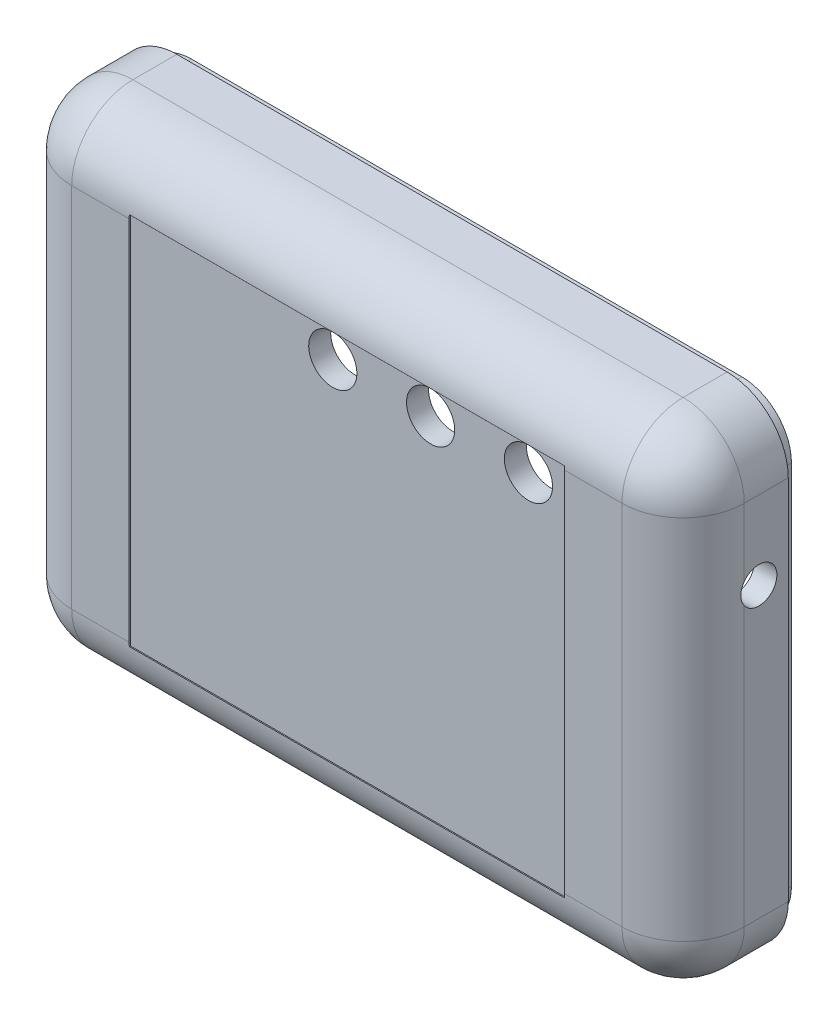
SolidWorks part; units mm, degrees
material "ABS"
ref_plane "Front Plane" through (0, 0, 0) normal (0, 0, 1) x (1, 0, 0)
ref_plane "Top Plane" through (0, 0, 0) normal (0, 1, 0) x (1, 0, 0)
ref_plane "Right Plane" through (0, 0, 0) normal (1, 0, 0) x (0, 0, -1)
ref_plane "Plane1" through (0, 0, 9.652) normal (0, 0, -1) x (-1, 0, 0)
sketch "Sketch1" plane through (0, 0, 9.652) normal (0, 0, -1) x (-1, 0, 0)
  line L0 (-146.2852, 11.5363) -> (-76.4352, 11.5363)
  line L1 (-76.4352, 11.5363) -> (-76.4352, 62.3363)
  line L2 (-76.4352, 62.3363) -> (-146.2852, 62.3363)
  line L3 (-146.2852, 62.3363) -> (-146.2852, 11.5363)
extrude "Boss-Extrude1" add sketch "Sketch1" against normal blind 10.922
sketch "Sketch2" plane through (0, 0, 9.652) normal (0, 0, -1) x (-1, 0, 0)
  line L0 (-77.629, 23.0298) -> (-77.629, 12.7301)
  line L1 (-77.629, 12.7301) -> (-145.0914, 12.7301)
  line L2 (-145.0914, 12.7301) -> (-145.0914, 61.1425)
  line L3 (-145.0914, 61.1425) -> (-77.629, 61.1425)
  line L4 (-77.629, 61.1425) -> (-77.629, 54.7798)
  line L5 (-77.629, 54.7798) -> (-143.9484, 54.7798)
  line L6 (-143.9484, 54.7798) -> (-143.9484, 23.0298)
  line L7 (-143.9484, 23.0298) -> (-77.629, 23.0298)
extrude "Boss-Extrude2" add sketch "Sketch2" along normal blind 1.524
ref_plane "Plane2" through (0, 0, 16.764) normal (0, 0, 1) x (1, 0, 0)
sketch "Sketch4" plane through (0, 0, 16.764) normal (0, 0, 1) x (1, 0, 0)
  line L0 (143.9484, 54.7798) -> (76.4352, 54.7798)
  line L1 (76.4352, 54.7798) -> (76.4352, 23.0298)
  line L2 (76.4352, 23.0298) -> (143.9484, 23.0298)
  line L3 (143.9484, 23.0298) -> (143.9484, 54.7798)
extrude "Cut-Extrude1" cut sketch "Sketch4" against normal up to surface up to plane "Plane1"
sketch "Sketch5" plane through (0, 0, 16.764) normal (0, 0, -1) x (-1, 0, 0)
  line L0 (-143.9484, 54.7798) -> (-143.9484, 23.0298)
  line L1 (-143.9484, 23.0298) -> (-78.772, 23.0298)
  line L2 (-78.772, 23.0298) -> (-78.772, 54.7798)
  line L3 (-78.772, 54.7798) -> (-143.9484, 54.7798)
extrude "Cut-Extrude2" cut sketch "Sketch5" against normal blind 1.397
ref_plane "Plane3" through (0, 13.8731, 0) normal (0, -1, 0) x (1, 0, 0)
sketch "Sketch6" plane through (0, 13.8731, 0) normal (0, -1, 0) x (1, 0, 0)
  line L0 (78.772, 8.128) -> (143.9484, 8.128)
  line L1 (143.9484, 8.128) -> (143.9484, 18.161)
  line L2 (143.9484, 18.161) -> (78.772, 18.161)
  line L3 (78.772, 18.161) -> (78.772, 8.128)
extrude "Cut-Extrude3" cut sketch "Sketch6" against normal up to next
ref_plane "Plane4" through (0, 59.9995, 0) normal (0, 1, 0) x (1, 0, 0)
sketch "Sketch7" plane through (0, 59.9995, 0) normal (0, 1, 0) x (1, 0, 0)
  line L0 (78.772, -18.161) -> (143.9484, -18.161)
  line L1 (143.9484, -18.161) -> (143.9484, -8.128)
  line L2 (143.9484, -8.128) -> (78.772, -8.128)
  line L3 (78.772, -8.128) -> (78.772, -18.161)
extrude "Cut-Extrude4" cut sketch "Sketch7" against normal up to next
sketch "Sketch8" plane through (0, 0, 20.574) normal (0, 0, 1) x (1, 0, 0)
  line L0 (133.9662, 56.3673) -> (88.7542, 56.3673)
  line L1 (88.7542, 56.3673) -> (88.7542, 17.5053)
  line L2 (88.7542, 17.5053) -> (133.9662, 17.5053)
  line L3 (133.9662, 17.5053) -> (133.9662, 56.3673)
extrude "Cut-Extrude5" cut sketch "Sketch8" against normal blind 0.127
ref_plane "Plane5" through (0, 19.4738, 0) normal (0, -1, 0) x (1, 0, 0)
sketch "Sketch9" plane through (0, 19.4738, 0) normal (0, -1, 0) x (1, 0, 0)
  line L0 (86.7603, 18.161) -> (84.3727, 18.161)
  line L1 (84.3727, 18.161) -> (84.3727, 8.89)
  line L2 (84.3727, 8.89) -> (86.7603, 8.89)
  line L3 (86.7603, 8.89) -> (86.7603, 18.161)
  line L4 (84.3727, 18.161) -> (84.3727, 8.89) construction
revolve "Revolve1" add sketch "Sketch9" angle 360 about L4 reverse direction yes
ref_plane "Plane6" through (0, 54.3988, 0) normal (0, -1, 0) x (1, 0, 0)
sketch "Sketch10" plane through (0, 54.3988, 0) normal (0, -1, 0) x (1, 0, 0)
  line L0 (140.7353, 18.161) -> (138.3477, 18.161)
  line L1 (138.3477, 18.161) -> (138.3477, 8.89)
  line L2 (138.3477, 8.89) -> (140.7353, 8.89)
  line L3 (140.7353, 8.89) -> (140.7353, 18.161)
  line L4 (138.3477, 18.161) -> (138.3477, 8.89) construction
revolve "Revolve2" add sketch "Sketch10" angle 360 about L4 reverse direction yes
hole_wizard "Hole1" positions "Sketch12" profile "Sketch11" legacy
sketch "Sketch12" plane through (0, 0, 18.161) normal (0, 0, -1) x (-1, 0, 0)
  point P0 (-130.0927, 53.7638)
  point P1 (-119.9327, 53.7638)
  point P2 (-109.7727, 53.7638)
sketch "Sketch11" plane through (130.0927, 53.7638, 18.161) normal (1, 0, 0) x (0, 1, 0)
  line L0 (0, 0) -> (0, 2.413)
  line L1 (0, 2.413) -> (2.5019, 2.413)
  line L2 (2.5019, 2.413) -> (2.5019, 0)
  line L3 (2.5019, 0) -> (0, 0)
  line L4 (0, 110) -> (0, -10) construction
  dimension "Diameter" = 5.0038
  dimension "Depth" = 2.413
hole_wizard "M2 Clearance Hole1" positions "Sketch14" profile "Sketch13" hole size "M2" standard "ANSI Metric"
sketch "Sketch14" plane through (0, 0, 8.89) normal (0, 0, -1) x (-1, 0, 0)
  point P0 (-138.3477, 54.3988)
  point P1 (-84.3727, 19.4738)
sketch "Sketch13" plane through (138.3477, 54.3988, 8.89) normal (1, 0, 0) x (0, 1, 0)
  line L0 (0, 0) -> (0, 9.271)
  line L1 (0, 9.271) -> (1.143, 9.271)
  line L2 (1.143, 9.271) -> (1.143, 0)
  line L5 (1.143, 0) -> (0, 0)
  line L10 (0, 9.271) -> (-1.143, 9.271) construction
  line L11 (0, -6.35) -> (0, 107.95) construction
  dimension "Hole Dia." = 2.286
  dimension "Hole Depth" = 9.271
  dimension "Drill Angle" = 180
hole_wizard "M3.5 Clearance Hole1" positions "Sketch16" profile "Sketch15" hole size "M3.5" standard "ANSI Metric"
sketch "Sketch16" plane through (143.9484, 0, 0) normal (-1, 0, 0) x (0, 0, 1)
  point P0 (12.7, 47.8583)
sketch "Sketch15" plane through (143.9484, 47.8583, 12.7) normal (0, 1, 0) x (0, 0, 1)
  line L0 (0, 0) -> (0, 2.3368)
  line L1 (0, 2.3368) -> (1.8669, 2.3368)
  line L2 (1.8669, 2.3368) -> (1.8669, 0)
  line L5 (1.8669, 0) -> (0, 0)
  line L11 (0, -6.35) -> (0, 107.95) construction
  dimension "Thru Hole Dia." = 3.7338
  dimension "Thru Hole Depth" = 2.3368
fillet "Fillet1" radius 4.0132 4 edges at (78.772, 13.8731, 13.1445) (143.9484, 59.9995, 13.1445) (78.772, 59.9995, 13.1445) (143.9484, 13.8731, 13.1445) tangent propagation no
fillet "Fillet2" radius 1.27 8 edges at (142.7729, 15.0486, 18.161) (143.9484, 36.9363, 18.161) (111.3602, 13.8731, 18.161) (142.7729, 58.8241, 18.161) (79.9474, 15.0486, 18.161) (111.3602, 59.9995, 18.161) (78.772, 36.9363, 18.161) (79.9474, 58.8241, 18.161) tangent propagation no
fillet "Fillet3" radius 5.1562 4 edges at (77.629, 61.1425, 8.89) (145.0914, 61.1425, 8.89) (77.629, 12.7301, 8.89) (145.0914, 12.7301, 8.89) tangent propagation no
fillet "Fillet4" radius 6.35 8 edges at (146.2852, 62.3363, 15.113) (76.4352, 62.3363, 15.113) (111.3602, 62.3363, 20.574) (146.2852, 11.5363, 15.113) (76.4352, 11.5363, 15.113) (146.2852, 36.9363, 20.574) (76.4352, 36.9363, 20.574) (111.3602, 11.5363, 20.574)
